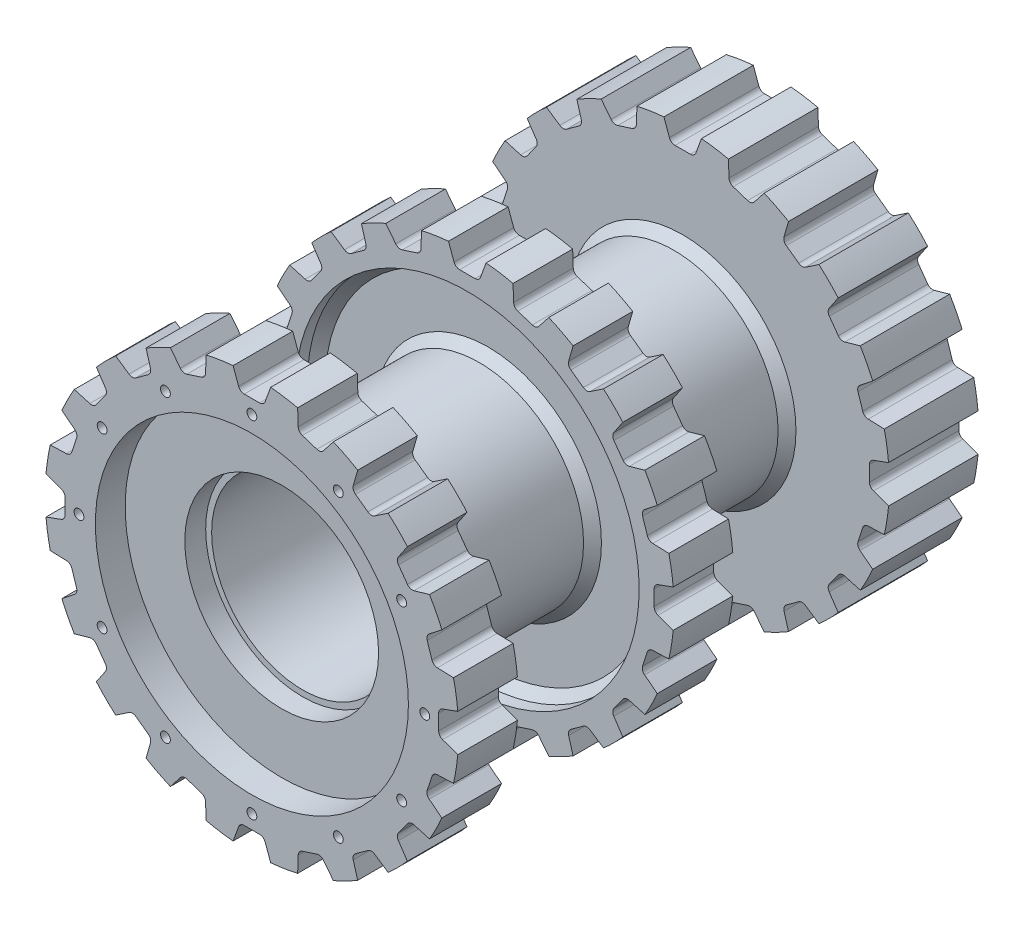
SolidWorks part; units mm, degrees
material "7079 Alloy"
ref_plane "Front" through (0, 0, 0) normal (0, 0, 1) x (1, 0, 0)
ref_plane "Top" through (0, 0, 0) normal (0, 1, 0) x (1, 0, 0)
ref_plane "Right" through (0, 0, 0) normal (1, 0, 0) x (0, 0, -1)
sketch "Sketch1" plane through (0, 0, 0) normal (0, 0, 1) x (1, 0, 0)
  circle A0 centre (0, 0) radius 69.3444
  dimension "D1" = 138.6887
extrude "Base-Extrude" add sketch "Sketch1" along normal mid plane 174.5
sketch "Sketch2" plane through (0, 0, 0) normal (0, 0, 1) x (1, 0, 0)
  line L0 (0, 0) -> (0, 56.1155) construction
  line L1 (-6.3, 69.0576) -> (-3.9706, 62.6576)
  line L2 (-3.9706, 62.6576) -> (3.9706, 62.6576)
  line L3 (3.9706, 62.6576) -> (6.3, 69.0576)
  circle A0 centre (0, 0) radius 69.3444 construction
  dimension "D1" = 12.6
  dimension "D2" = 6.3
  dimension "D3" = 6.4
  dimension "D4" = 40
  dimension "D5" = 20
extrude "Cut-Extrude1" cut sketch "Sketch2" against normal through all and the other way through all
fillet "Fillet1" radius 2 2 edges at (-3.9706, 62.6576, 0) (3.9706, 62.6576, 0)
ref_axis "PulleyAxis" through (0, 0, -95.975) along (0, 0, 1)
pattern_circular "CirPattern1" count 20 every 18 about axis through (0, 0, -95.975) along (0, 0, 1) of "Fillet1", "Cut-Extrude1"
ref_plane "Plane1" through (488.95, 0, 0) normal (1, 0, 0) x (0, 0, -1)
ref_axis "AxisDistance" through (488.95, 0, 95.975) along (0, 0, -1)
sketch "Sketch3" plane through (0, 0, 87.25) normal (0, 0, 1) x (1, 0, 0)
  circle A0 centre (0, 0) radius 30.5
  dimension "D1" = 61
extrude "Cut-Extrude2" cut sketch "Sketch3" against normal blind 200
sketch "Sketch4" plane through (0, 0, 87.25) normal (0, 0, 1) x (1, 0, 0)
  circle A0 centre (0, 0) radius 32.5
  dimension "D1" = 65
extrude "Cut-Extrude3" cut sketch "Sketch4" against normal blind 17
sketch "Sketch5" plane through (0, 0, -87.25) normal (0, 0, -1) x (-1, 0, 0)
  circle A0 centre (0, 0) radius 32.5
  dimension "D1" = 65
extrude "Cut-Extrude4" cut sketch "Sketch5" against normal blind 27
sketch "Sketch7" plane through (0, 0, -87.25) normal (0, 0, -1) x (-1, 0, 0)
  circle A2 centre (0, 0) radius 52.5
  dimension "D1" = 105
extrude "Cut-Extrude6" cut sketch "Sketch7" against normal blind 20
sketch "Sketch12" plane through (0, 0, 87.25) normal (0, 0, 1) x (1, 0, 0)
  circle A0 centre (0, 0) radius 52.5
  dimension "D1" = 105
extrude "Cut-Extrude8" cut sketch "Sketch12" against normal blind 10
sketch "Sketch13" plane through (0, 0, 87.25) normal (0, 0, 1) x (1, 0, 0)
  line L0 (0, 0) -> (0, 58) construction
  circle A0 centre (0, 0) radius 58 construction
  circle A1 centre (0, 58) radius 1.65
  circle A2 centre (29, 50.2295) radius 1.65
  circle A3 centre (50.2295, 29) radius 1.65
  circle A4 centre (58, 0) radius 1.65
  circle A5 centre (50.2295, -29) radius 1.65
  circle A6 centre (29, -50.2295) radius 1.65
  circle A7 centre (0, -58) radius 1.65
  circle A8 centre (-29, -50.2295) radius 1.65
  circle A9 centre (-50.2295, -29) radius 1.65
  circle A10 centre (-58, 0) radius 1.65
  circle A11 centre (-50.2295, 29) radius 1.65
  circle A12 centre (-29, 50.2295) radius 1.65
  dimension "D1" = 116
  dimension "D2" = 3.3
  dimension "D3" = 12
extrude "Cut-Extrude9" cut sketch "Sketch13" against normal blind 15
ref_plane "Plane2" through (0, 0, 0) normal (0, 0, -1) x (-1, 0, 0)
mirror "Mirror1" about plane through (0, 0, 0) normal (0, 0, -1) of "Cut-Extrude9"
sketch "Sketch14" plane through (0, 0, 0) normal (0, 1, 0) x (1, 0, 0)
  line L0 (0, 0) -> (0, 87.25) construction
  line L1 (52.5, 87.25) -> (-52.5, 87.25) construction
  line L2 (32.5, 67.25) -> (-32.5, 67.25) construction
  line L3 (-100.1842, 57.25) -> (-35, 57.25)
  line L4 (-100.1842, 57.25) -> (-100.1842, 5)
  line L5 (-100.1842, 5) -> (-35, 5)
  line L6 (-35, 57.25) -> (-35, 5)
  line L7 (-99.2986, -15) -> (-35, -15)
  line L8 (-99.2986, -15) -> (-99.2986, -67.25)
  line L9 (-99.2986, -67.25) -> (-35, -67.25)
  line L10 (-35, -15) -> (-35, -67.25)
  line L11 (-32.5, -77.25) -> (32.5, -77.25) construction
  dimension "D1" = 10
  dimension "D2" = 35
  dimension "D3" = 10
  dimension "D4" = 20
revolve "Cut-Revolve1" cut sketch "Sketch14" angle 360 about L0
sketch "Sketch15" plane through (0, 0, 0) normal (0, 1, 0) x (1, 0, 0)
  line L0 (0, 0) -> (0, 95.9086) construction
  line L1 (-59.9942, -5) -> (9.158, -5) construction
  line L2 (-60.3851, 5) -> (-62.2175, 5) construction
  line L3 (-62.6576, 5) -> (-62.6576, -15) construction
  line L4 (-35, 8.6668) -> (-57.6576, 8.6668)
  line L5 (-35, 8.6668) -> (-35, -2)
  line L6 (-35, -2) -> (-57.6576, -2)
  line L7 (-57.6576, 8.6668) -> (-57.6576, -2)
  line L8 (-35, -18.6668) -> (-57.6576, -18.6668)
  line L9 (-57.6576, -18.6668) -> (-57.6576, -8)
  line L10 (-35, -8) -> (-57.6576, -8)
  line L11 (-35, -18.6668) -> (-35, -8)
  dimension "D1" = 10
  dimension "D2" = 35
  dimension "D3" = 5
  dimension "D4" = 6
revolve "Cut-Revolve2" cut sketch "Sketch15" angle 360 about L0
chamfer "Chamfer1" distance 3 angle 45 6 edges at (35, 0, -57.25) (35, 0, 67.25) (57.6576, 0, 2) (57.6576, 0, 8) (35, 0, 8) (35, 0, 2)
equation "\"D5@Sketch2\" = \"D4@Sketch2\"/2"
equation "\"D2@Sketch2\" = \"D1@Sketch2\"/2"
equation "\"D2@CirPattern1\"=360/\"D1@CirPattern1\""
equation "\"D1@Fillet2\" = \"D1@Boss-Extrude1\"/4"
equation "\"D1@Fillet3\" = \"D1@Boss-Extrude2\"/4"
